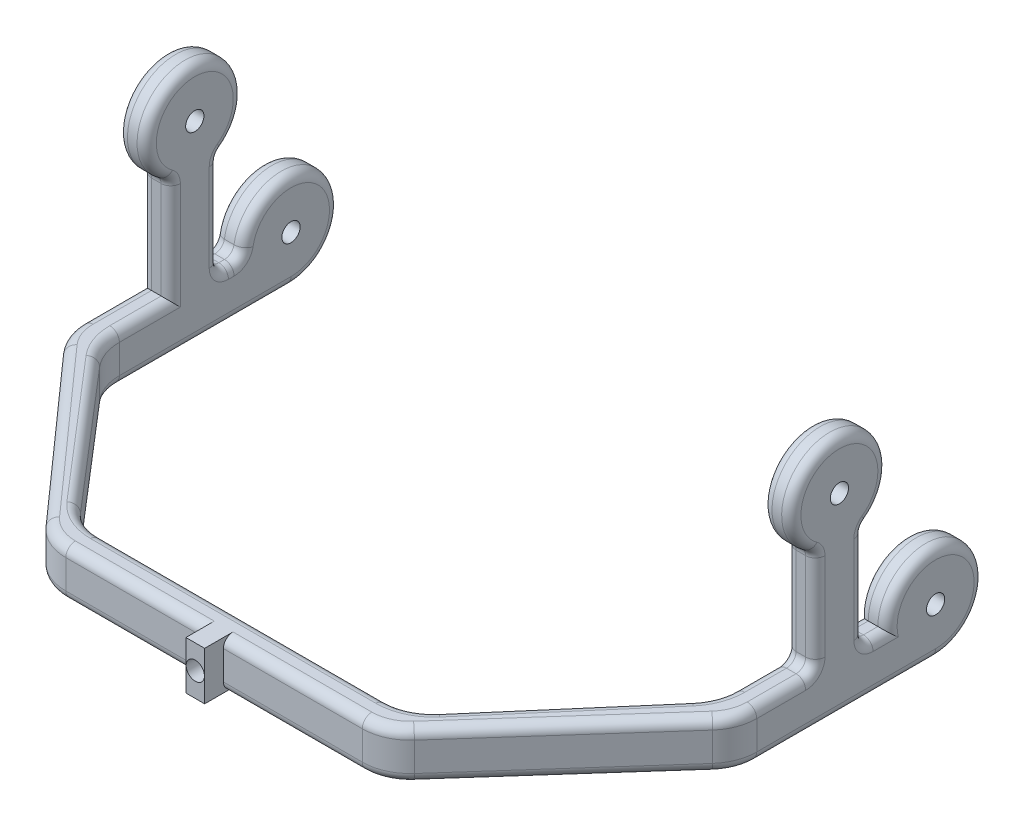
SolidWorks part; units mm, degrees
ref_plane "Front Plane" through (0, 0, 0) normal (0, 0, 1) x (1, 0, 0)
ref_plane "Top Plane" through (0, 0, 0) normal (0, 1, 0) x (1, 0, 0)
ref_plane "Right Plane" through (0, 0, 0) normal (1, 0, 0) x (0, 0, -1)
sketch "Sketch1" plane through (0, 0, 0) normal (0, 0, 1) x (1, 0, 0)
  line L1 (18, 5) -> (-18, 5)
  line L2 (18, 5) -> (18, -5)
  line L3 (18, -5) -> (-18, -5)
  line L4 (-18, 5) -> (-18, -5)
  line L5 (18, 5) -> (-18, -5) construction
  line L6 (18, -5) -> (-18, 5) construction
  point P0 (0, 0)
  dimension "D1" = 36
  dimension "D2" = 10
extrude "Boss-Extrude1" add sketch "Sketch1" along normal blind 6
sketch "Sketch2" plane through (0, 0, 6) normal (0, 0, 1) x (1, 0, 0)
  line L0 (-18, 0) -> (18, 0) construction
  line L1 (-18, 5) -> (-18, -5) construction
  line L2 (18, -5) -> (18, 5) construction
  line L3 (18, 5) -> (-18, 5) construction
  line L4 (-18, -1.9) -> (-1.9, -1.9)
  line L5 (-18, -1.9) -> (-18, 1.9)
  line L6 (-18, 1.9) -> (-1.9, 1.9)
  line L7 (18, -1.9) -> (18, 1.9)
  line L8 (-18, -1.9) -> (18, 1.9) construction
  line L9 (-18, 1.9) -> (18, -1.9) construction
  line L10 (-1.9, -5) -> (1.9, -5)
  line L11 (-1.9, -5) -> (-1.9, -1.9)
  line L12 (-1.9, 5) -> (1.9, 5)
  line L13 (1.9, -5) -> (1.9, -1.9)
  line L14 (-1.9, -5) -> (1.9, 5) construction
  line L15 (-1.9, 5) -> (1.9, -5) construction
  line L16 (-18, -5) -> (18, -5) construction
  line L19 (1.9, -1.9) -> (18, -1.9)
  line L20 (1.9, 1.9) -> (1.9, 5)
  line L21 (1.9, 1.9) -> (18, 1.9)
  line L22 (-1.9, 1.9) -> (-1.9, 5)
  point P6 (0, 0)
  point P12 (0, 0)
  dimension "D1" = 3.8
  dimension "D2" = 3.8
extrude "Boss-Extrude2" add sketch "Sketch2" along normal blind 3.8
sketch "Sketch3" plane through (0, 0, 0) normal (0, 0, -1) x (-1, 0, 0)
  line L0 (18, 5) -> (-18, -5) construction
  line L1 (-18, -5) -> (18, -5) construction
  line L2 (18, -5) -> (-18, 5) construction
  line L3 (-18, -5) -> (-18, 5) construction
  line L4 (-18, 5) -> (18, 5) construction
  circle A0 centre (0, 0) radius 1.9
  dimension "D1" = 3.8
sketch "Sketch5" plane through (0, 5, 0) normal (0, 1, 0) x (1, 0, 0)
  line L0 (0, -9.8) -> (0, 18.0299) construction
  line L1 (1.9, -9.8) -> (-1.9, -9.8) construction
  line L5 (18, -6) -> (18, 0) construction
  line L6 (18, -6) -> (1.9, -6) construction
  line L7 (18, -6) -> (18, 0)
  line L8 (18, -6) -> (35.3029, -6)
  line L11 (70, 33.0207) -> (70, 74)
  line L12 (70, 74) -> (64, 74)
  line L13 (64, 74) -> (64, 34.6151)
  line L16 (34.2552, 0) -> (18, 0)
  line L17 (18, -6) -> (1.9, -6) construction
  line L18 (70, 33.0207) -> (64, 34.6151) construction
  line L21 (-64, 74) -> (-64, 34.6151)
  line L22 (-70, 74) -> (-64, 74)
  line L23 (-70, 33.0207) -> (-70, 74)
  line L26 (-18, -6) -> (-35.3029, -6)
  line L27 (-18, -6) -> (-18, 0)
  line L28 (-34.2552, 0) -> (-18, 0)
  line L29 (64, 34.6151) -> (34.2552, 0)
  line L30 (70, 33.0207) -> (35.3029, -6)
  line L31 (-64, 34.6151) -> (-34.2552, 0)
  line L32 (-35.3029, -6) -> (-70, 33.0207)
  dimension "D1" = 80
  dimension "D2" = 140
  dimension "D3" = 6
extrude "Boss-Extrude3" add sketch "Sketch5" against normal blind 10
sketch "Sketch6" plane through (0, 0, -74) normal (0, 0, -1) x (-1, 0, 0)
  line L0 (-67, 5) -> (-67, -5) construction
  line L1 (-70, 5) -> (-64, 5) construction
  line L2 (-70, -5) -> (-64, -5) construction
sketch "Sketch7" plane through (0, 5, 0) normal (0, 1, 0) x (1, 0, 0)
  line L0 (67, 74) -> (67, 41.0807) construction
  line L1 (70, 74) -> (64, 74) construction
ref_plane "Plane2" through (67, 0, 0) normal (-1, 0, 0) x (0, 0, 1)
sketch "Sketch8" plane through (67, 0, 0) normal (-1, 0, 0) x (0, 0, 1)
  line L0 (-74, 5) -> (-41.0807, 5) construction
  line L1 (-59, 5) -> (-49, 5)
  line L2 (-59, 5) -> (-59, 35)
  line L3 (-59, 35) -> (-49, 35)
  line L4 (-49, 5) -> (-49, 35)
  line L5 (-74, 5) -> (-74, -5) construction
  dimension "D1" = 15
  dimension "D2" = 10
  dimension "D3" = 30
extrude "Boss-Extrude4" add sketch "Sketch8" along direction (-1, 0, 0) on the side of the normal blind 3 and the other way blind 3 contours L2 L1 L4 L3
sketch "Sketch10" plane through (0, 0, -74) normal (0, 0, -1) x (-1, 0, 0)
  line L0 (67, -5) -> (67, 5) construction
  line L1 (64, -5) -> (70, -5) construction
  line L2 (64, 5) -> (70, 5) construction
sketch "Sketch11" plane through (0, 5, 0) normal (0, 1, 0) x (1, 0, 0)
  line L0 (-67, 74) -> (-67, 46.0217) construction
ref_plane "Plane3" through (-67, 0, 0) normal (1, 0, 0) x (0, 0, -1)
sketch "Sketch12" plane through (-67, 0, 0) normal (1, 0, 0) x (0, 0, -1)
  line L0 (74, 5) -> (46.0217, 5) construction
  line L1 (59, 5) -> (49, 5)
  line L2 (59, 5) -> (59, 35)
  line L3 (59, 35) -> (49, 35)
  line L4 (49, 5) -> (49, 35)
  line L5 (74, -5) -> (74, 5) construction
  dimension "D1" = 15
  dimension "D2" = 10
  dimension "D3" = 30
extrude "Boss-Extrude5" add sketch "Sketch12" along normal blind 3 and the other way blind 3
sketch "Sketch13" plane through (64, 0, 0) normal (-1, 0, 0) x (0, 0, 1)
  line L0 (-59, 35) -> (-49, 35) construction
  circle A0 centre (-74, 5) radius 10
  circle A1 centre (-54, 35) radius 10
  dimension "D1" = 20
extrude "Boss-Extrude6" add sketch "Sketch13" against normal blind 6
sketch "Sketch14" plane through (-64, 0, 0) normal (1, 0, 0) x (0, 0, -1)
  line L0 (59, 35) -> (49, 35) construction
  circle A0 centre (74, 5) radius 10
  circle A1 centre (54, 35) radius 10
  dimension "D1" = 20
extrude "Boss-Extrude7" add sketch "Sketch14" against normal blind 6
sketch "Sketch15" plane through (-64, 0, 0) normal (1, 0, 0) x (0, 0, -1)
  circle A0 centre (54, 35) radius 1.9
  dimension "D1" = 3.8
extrude "Cut-Extrude2" cut sketch "Sketch15" against normal through all both and the other way through all
sketch "Sketch16" plane through (-64, 0, 0) normal (1, 0, 0) x (0, 0, -1)
  circle A0 centre (74, 5) radius 1.9
  dimension "D1" = 3.8
extrude "Cut-Extrude3" cut sketch "Sketch16" against normal through all both and the other way through all
fillet "Fillet1" radius 10 4 edges at (64, 0, -34.6151) (34.2552, 0, 0) (-34.2552, 0, 0) (-64, 0, -34.6151)
fillet "Fillet2" radius 10 4 edges at (-70, 0, -33.0207) (70, 0, -33.0207) (35.3029, 0, 6) (-35.3029, 0, 6)
sketch "Sketch17" plane through (0, 5, 0) normal (0, 1, 0) x (1, 0, 0)
  line L1 (-30.8133, -6) -> (33.5589, -6)
  line L2 (-30.8133, -6) -> (-30.8133, -17.0622)
  line L3 (-30.8133, -17.0622) -> (33.5589, -17.0622)
  line L4 (33.5589, -6) -> (33.5589, -17.0622)
extrude "Cut-Extrude4" cut sketch "Sketch17" against normal blind 10
sketch "Sketch21" plane through (0, 0, 6) normal (0, 0, 1) x (1, 0, 0)
  line L0 (-30.8133, -5) -> (30.8133, 5) construction
  line L1 (30.8133, 5) -> (30.8133, -5) construction
  line L2 (30.8133, -5) -> (-30.8133, 5) construction
  line L3 (-30.8133, -5) -> (30.8133, -5) construction
  line L4 (-1.95, 5) -> (1.95, 5)
  line L5 (-1.95, 5) -> (-1.95, -5)
  line L6 (-1.95, -5) -> (1.95, -5)
  line L7 (1.95, 5) -> (1.95, -5)
  line L8 (-1.95, 5) -> (1.95, -5) construction
  line L9 (-1.95, -5) -> (1.95, 5) construction
  point P4 (0, 0)
  dimension "D1" = 3.9
extrude "Boss-Extrude8" add sketch "Sketch21" along normal blind 3.9
sketch "Sketch23" plane through (0, 0, 0) normal (0, 0, -1) x (-1, 0, 0)
  circle A0 centre (0, 0) radius 1.9
  dimension "D1" = 3.8
extrude "Cut-Extrude11" cut sketch "Sketch23" against normal through all both and the other way through all
fillet "Fillet4" radius 2 62 edges at (-70, 15.6699, -49) (-64, 15.6699, -49) (-70, 15.6699, -59) (-64, 15.6699, -59) (70, 5, -61.5) (64, 5, -61.5) (64, 12.0711, -81.0711) (64, -5, -56.1607) (63.3767, -5, -34.8461) (49.4162, -5, -17.6434) (33.8363, -5, -0.9123) (0, -5, 0) (-33.8363, -5, -0.9123) (-64, 12.0711, -81.0711) (-64, -5, -56.1607) (-63.3767, -5, -34.8461) (63.3767, 5, -34.8461) (49.4162, 5, -17.6434) (33.8363, 5, -0.9123) (-64, 5, -43.6607) (-63.3767, 5, -34.8461) (-49.4162, 5, -17.6434) (-33.8363, 5, -0.9123) (70, 12.0711, -81.0711) (70, -5, -55.4118) (69.3469, -5, -33.2691) (52.8796, -5, -13.7669) (34.909, -5, 5.1228) (-70, 12.0711, -81.0711) (-70, -5, -55.4118) (-69.3469, -5, -33.2691) (-52.8796, -5, -13.7669) (-34.909, -5, 5.1228) (-70, 5, -42.9118) (-69.3469, 5, -33.2691) (-52.8796, 5, -13.7669) (-34.909, 5, 5.1228) (69.3469, 5, -33.2691) (52.8796, 5, -13.7669) (34.909, 5, 5.1228) (-67, 26.3397, -49) (-70, 45, -54) (-67, 26.3397, -59) (-64, 45, -54) (-67, 5, -59) (-70, 5, -61.5) (-67, 5, -64) (-64, 5, -61.5) (67, 5, -59) (70, 15.6699, -59) (67, 26.3397, -59) (64, 15.6699, -59) (70, 15.6699, -49) (67, 5, -49) (64, 15.6699, -49) (67, 26.3397, -49) (64, 45, -54) (70, 45, -54) (-49.4162, -5, -17.6434) (0, 5, 0) (-16.3816, -5, 6) (-16.3816, 5, 6)
